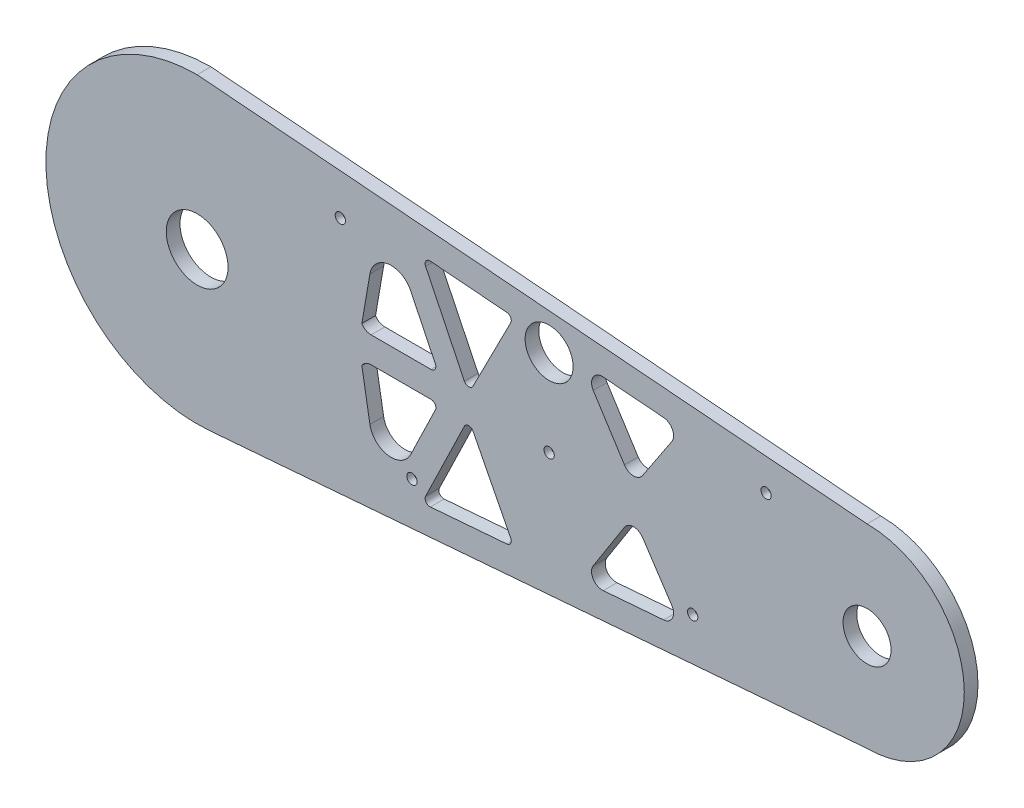
SolidWorks part; units mm, degrees
other "Marca1"
sketch "Croquis3" plane through (-70, -70, 6.35) normal (0, 0, 1) x (1, 0, 0)
material "6061-O (SS)"
ref_plane "Front Plane" through (0, 0, 0) normal (0, 0, 1) x (1, 0, 0)
ref_plane "Top Plane" through (0, 0, 0) normal (0, 1, 0) x (1, 0, 0)
ref_plane "Right Plane" through (0, 0, 0) normal (1, 0, 0) x (0, 0, -1)
sketch "Sketch1" plane through (0, 0, 0) normal (0, 0, 1) x (1, 0, 0)
  line L0 (0, 70) -> (310, 45)
  line L1 (5.1714, -69.8087) -> (310, -45)
  line L2 (0, 0) -> (310, 0) construction
  line L3 (107.899, 49.2595) -> (143.3142, 46.4034)
  line L4 (80.4851, 6) -> (108.233, 6)
  line L5 (219.6238, 32.8105) -> (206.1309, 12.4175)
  line L6 (197.7459, 12.4871) -> (183.2969, 35.1335)
  line L7 (162.8785, 6) -> (162.8785, -6) construction
  line L8 (258.6323, 64.5867) -> (258.6323, 39.5867) construction
  line L9 (145.1193, 43.1678) -> (127.6446, 8.9864)
  line L10 (123.6548, 9.0293) -> (105.7143, 46.0668)
  line L11 (104.0161, 49.5726) -> (42.0027, 49.5726) construction
  line L12 (187.9139, 42.8067) -> (215.8558, 40.5533)
  line L13 (162.8785, 44.8257) -> (162.8785, 6) construction
  line L14 (67.1248, 64.5867) -> (162.8785, 40) construction
  line L15 (201.8849, 6) -> (201.8849, 41.68) construction
  line L16 (125.6066, 5) -> (125.6066, 47.8315) construction
  line L17 (98.7975, 32.8194) -> (110.2385, 9.1999)
  line L18 (125.6066, -5) -> (125.6066, -47.8315) construction
  line L19 (201.8849, -6) -> (201.8849, -41.68) construction
  line L20 (162.8785, -44.8257) -> (162.8785, -6) construction
  line L21 (104.0161, -49.5726) -> (42.0027, -49.5726) construction
  line L22 (98.7975, -32.8194) -> (110.2385, -9.1999)
  line L23 (67.1248, 64.5867) -> (409.6974, 64.5867) construction
  line L24 (187.9139, -42.8067) -> (215.8558, -40.5533)
  line L25 (123.6548, -9.0293) -> (105.7143, -46.0668)
  line L26 (145.1193, -43.1678) -> (127.6446, -8.9864)
  line L27 (162.8785, 0) -> (258.6323, 64.5867) construction
  line L28 (67.1248, 64.5867) -> (67.1248, 39.5867) construction
  line L29 (197.7459, -12.4871) -> (183.2969, -35.1335)
  line L30 (219.6238, -32.8105) -> (206.1309, -12.4175)
  line L31 (80.4851, -6) -> (108.233, -6)
  line L32 (107.899, -49.2595) -> (143.3142, -46.4034)
  line L33 (0, -6.35) -> (0, 6.35) construction
  line L34 (67.1248, 39.5867) -> (162.8785, 40) construction
  line L35 (162.8785, 40) -> (68.3705, 24.1395) construction
  line L36 (79.9417, 30.1512) -> (76.2106, 8.4059)
  line L37 (79.9417, -30.1512) -> (76.2106, -8.4059)
  arc A0 (76.2106, 8.4059) -> (80.4851, 6) centre (80.4851, 11) ccw
  arc A1 (310, -45) -> (310, 45) centre (310, 0) ccw
  circle A2 centre (0, 0) radius 14.2938
  circle A3 centre (310, 0) radius 11.11
  arc A4 (79.9417, 30.1512) -> (98.7975, 32.8194) centre (89.7977, 28.4601) cw
  arc A5 (79.9417, -30.1512) -> (98.7975, -32.8194) centre (89.7977, -28.4601) ccw
  arc A6 (0, 70) -> (5.1714, -69.8087) centre (0, 0) ccw
  arc A7 (187.9139, 42.8067) -> (183.2969, 35.1335) centre (187.512, 37.8229) ccw
  arc A8 (219.6238, 32.8105) -> (215.8558, 40.5533) centre (215.4539, 35.5695) ccw
  arc A9 (206.1309, 12.4175) -> (197.7459, 12.4871) centre (201.961, 15.1765) cw
  circle A10 centre (162.8785, 40) radius 11.1125
  arc A13 (108.233, 6) -> (110.2385, 9.1999) centre (108.233, 8.2285) ccw
  arc A14 (123.6548, 9.0293) -> (127.6446, 8.9864) centre (125.6604, 10.0008) ccw
  arc A15 (145.1193, 43.1678) -> (143.3142, 46.4034) centre (143.1351, 44.1822) ccw
  arc A16 (107.899, 49.2595) -> (105.7143, 46.0668) centre (107.7198, 47.0383) ccw
  arc A17 (107.899, -49.2595) -> (105.7143, -46.0668) centre (107.7198, -47.0383) cw
  arc A18 (145.1193, -43.1678) -> (143.3142, -46.4034) centre (143.1351, -44.1822) cw
  arc A19 (123.6548, -9.0293) -> (127.6446, -8.9864) centre (125.6604, -10.0008) cw
  arc A20 (108.233, -6) -> (110.2385, -9.1999) centre (108.233, -8.2285) cw
  arc A24 (206.1309, -12.4175) -> (197.7459, -12.4871) centre (201.961, -15.1765) ccw
  arc A25 (219.6238, -32.8105) -> (215.8558, -40.5533) centre (215.4539, -35.5695) cw
  arc A26 (187.9139, -42.8067) -> (183.2969, -35.1335) centre (187.512, -37.8229) cw
  arc A29 (76.2106, -8.4059) -> (80.4851, -6) centre (80.4851, -11) cw
  point P31 (177.8851, 43.6155)
  point P42 (187.6504, 6)
  point P44 (85.2119, 60.8662)
  point P45 (138.1067, 6)
  point P79 (85.2119, -60.8662)
  point P100 (138.1067, -6)
  point P101 (187.6504, -6)
  point P102 (177.8851, -43.6155)
  point P104 (0, 0)
  point P114 (310, 0)
  point P119 (0.2114, 0.3175)
  dimension "D2" = 45
  dimension "D3" = 12.7
  dimension "D4" = 22.22
  dimension "D6" = 12
  dimension "D11" = 5
  dimension "D12" = 70
  dimension "D13" = 25
  dimension "D8" = 5
  dimension "D14" = 12
  dimension "D15" = 25
  dimension "D16" = 310
  dimension "D17" = 22.225
  dimension "D5" = 28.5877
  dimension "D19" = 10
  dimension "D20" = 10
  dimension "D7" = 6
  dimension "D9" = 9.279
  dimension "D10" = 34
  dimension "D18" = 40
extrude "Boss-Extrude1" add sketch "Sketch1" along normal blind 6.35
sketch "Sketch2" plane through (0, 0, 6.35) normal (0, 0, 1) x (1, 0, 0)
  line L0 (263.0927, 39.4927) -> (-0.4655, 64.9983)
  line L1 (4.6885, -64.8307) -> (263.1366, -39.5384)
  arc A0 (-0.4655, 64.9983) -> (4.6885, -64.8307) centre (0, 0) ccw
  arc A1 (263.1366, -39.5384) -> (270.3186, -23.7999) centre (262.1626, -29.5859) ccw
  circle A2 centre (0, 0) radius 40
  arc A3 (270.292, 23.7623) -> (270.3186, -23.7999) centre (303.867, 0) ccw
  arc A4 (270.292, 23.7623) -> (263.0927, 39.4927) centre (262.1295, 29.5392) ccw
  dimension "D1" = 10
  dimension "D2" = 41.133
  dimension "D3" = 65
ref_plane "Plane1" through (0, 0, 10) normal (0, 0, 1) x (1, 0, 0)
sketch "Croquis1" plane through (0, 0, 6.35) normal (0, 0, 1) x (1, 0, 0)
  line L0 (99.4174, -42.273) -> (229.2992, -31.7024) construction
  line L1 (5.1714, -69.8087) -> (310, -45) construction
  line L2 (99.4174, -61.323) -> (229.2992, -50.7524) construction
  circle A1 centre (99.4174, -42.273) radius 2.3813
  circle A2 centre (229.2992, -31.7024) radius 2.3813
  circle A3 centre (99.4174, -42.273) radius 19.05 construction
  circle A4 centre (229.2992, -31.7024) radius 19.05 construction
  point P20 (0, 0)
  dimension "D5" = 4.7625
  dimension "D1" = 4.7625
  dimension "D3" = 38.1
  dimension "D4" = 38.1
  dimension "D2" = 19.8
extrude "Cortar-Extruir1" cut sketch "Croquis1" against normal blind 50
sketch "Croquis4" plane through (0, 0, 0) normal (0, 0, -1) x (-1, 0, 0)
  circle A0 centre (-229.2992, -31.7024) radius 5
  circle A1 centre (-99.4174, -42.273) radius 5
  dimension "D1" = 10
extrude "Cortar-Extruir2" cut sketch "Croquis4" against normal blind 3.175
sketch "Croquis5" plane through (0, 0, 0) normal (0, 0, -1) x (-1, 0, 0)
  line L0 (-162.8785, 40) -> (-162.8785, -35.6506) construction
  line L1 (-193.2674, -35.6506) -> (-132.4897, -35.6506) construction
  circle A0 centre (-162.8785, 0) radius 5
  point P6 (-162.8785, -35.6506)
  dimension "D2" = 10
  dimension "D1" = 40
extrude "Cortar-Extruir3" cut sketch "Croquis5" against normal blind 3.175
sketch "Croquis6" plane through (0, 0, 0) normal (0, 0, -1) x (-1, 0, 0)
  circle A0 centre (-162.8785, 0) radius 2.3813
  dimension "D1" = 4.7625
extrude "Cortar-Extruir4" cut sketch "Croquis6" against normal blind 10
sketch "Croquis7" plane through (0, 0, 0) normal (0, 0, -1) x (-1, 0, 0)
  line L0 (-229.2992, -31.7024) -> (-99.4174, -42.273) construction
  line L1 (-99.4174, -42.273) -> (-66.2632, 45.6861) construction
  line L2 (-229.2992, -31.7024) -> (-263.2934, 34.0273) construction
  circle A0 centre (-66.2632, 45.6861) radius 2.3813
  circle A1 centre (-263.2934, 34.0273) radius 2.3813
  dimension "D5" = 4.7625
  dimension "D1" = 94
  dimension "D2" = 106
  dimension "D3" = 74
  dimension "D4" = 238
extrude "Cortar-Extruir5" cut sketch "Croquis7" against normal blind 10
sketch "Croquis8" plane through (0, 0, 0) normal (0, 0, -1) x (-1, 0, 0)
  circle A0 centre (-263.2934, 34.0273) radius 5
  circle A1 centre (-66.2632, 45.6861) radius 5
  dimension "D1" = 10
  dimension "D2" = 10
extrude "Cortar-Extruir6" cut sketch "Croquis8" against normal blind 3.16
